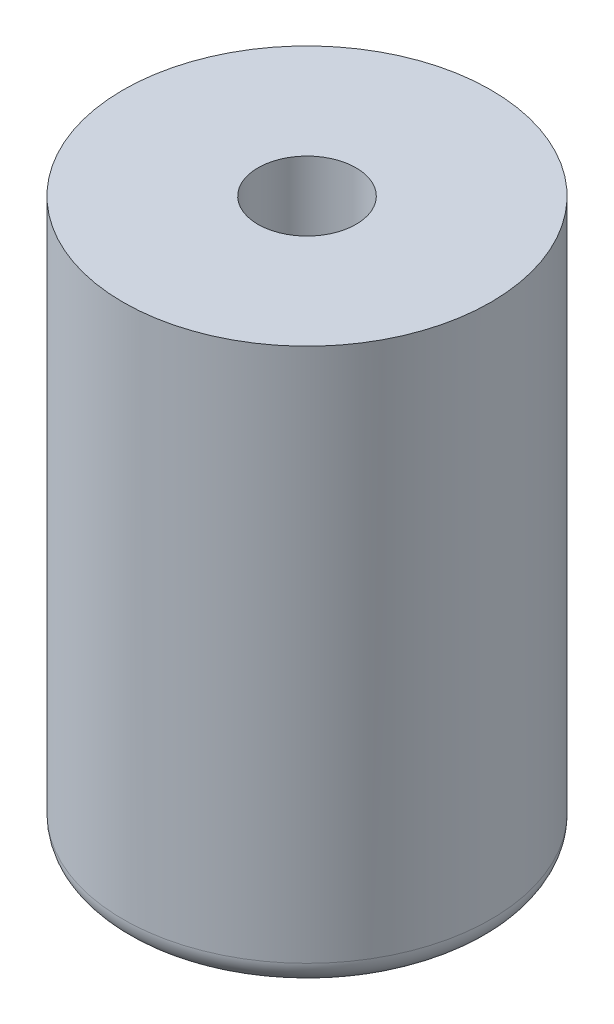
SolidWorks part; units mm, degrees
ref_plane "Front Plane" through (0, 0, 0) normal (0, 0, 1) x (1, 0, 0)
ref_plane "Top Plane" through (0, 0, 0) normal (0, 1, 0) x (1, 0, 0)
ref_plane "Right Plane" through (0, 0, 0) normal (1, 0, 0) x (0, 0, -1)
sketch "Sketch3" plane through (0, 0, 0) normal (0, 1, 0) x (1, 0, 0)
  line L0 (0, 0) -> (4.1384, 0) construction
sketch "Sketch4" plane through (0, 0, 0) normal (0, 1, 0) x (1, 0, 0)
  line L0 (0, 0) -> (0, 4.4358) construction
  line L1 (-0.3, 0.9539) -> (-0.3, 1.4697)
  line L2 (0.3, 1.4697) -> (0.3, 0.9539)
  arc A0 (-0.3, 0.9539) -> (0.3, 0.9539) centre (0, 0) ccw
  arc A1 (-0.3, 1.4697) -> (0.3, 1.4697) centre (0, 0) ccw
  circle A2 centre (0, 0) radius 0.4
  circle A3 centre (0, 0) radius 1.5
  circle A4 centre (0, 0) radius 0.8
  dimension "D1" = 0.5
  dimension "D4" = 1
  dimension "D2" = 0.6
  dimension "D3" = 0.3
extrude "Boss-Extrude3" add sketch "Sketch4" along normal blind 3 separate body contours A1 L0 A0 L1 | L0 A1 L2 A0 | A0 L2 A1 L1 region at (1.1292, 0, -0.922)
extrude "Boss-Extrude4" add sketch "Sketch4<3>" along normal blind 0.75 from offset 3 contours A1 L0 A0 L1 | L0 A0 L2 A3 A2 | L0 A3 L2 A0 | A4 L0 A0 L1 | L0 A4 L2 A0 | A0 L0 A2 A4 L1 region at (0.5497, 0, -0.5497) region at (0.1475, 0, -1.4606) region at (1.1292, 0, -0.922)
sketch "Sketch4<3>" plane through (0, 0, 0) normal (0, 1, 0) x (1, 0, 0) same geometry as "Sketch4"
extrude "Boss-Extrude5" add sketch "Sketch4<5>" along normal blind 1 from offset 3.75 contours A2 L0 | L0 A2 | L0 A3 L2 A4 | A1 L0 A4 L1 | A4 L0 A3 L1 | L0 A4 L2 A3 | A4 region at (0.1475, 0, -1.4606) region at (0.2748, 0, -0.2748) region at (1.1292, 0, -0.922)
sketch "Sketch4<5>" plane through (0, 0, 0) normal (0, 1, 0) x (1, 0, 0) same geometry as "Sketch4"
fillet "Fillet6" radius 0.75 1 edges at (0, 0, 1)
fillet "Fillet7" radius 0.5 2 edges at (0.3, 0.3205, -1.0659) (0.3, 1.8536, -0.9539)
fillet "Fillet8" radius 0.5 2 edges at (-0.3, 0.252, -1.1142) (-0.3, 1.8536, -0.9539)
fillet "Fillet9" radius 0.2 5 edges at (-0.4036, 0.1625, -1.4447) (0.4749, 0.0901, -1.4228) (0, 0, 1.5)
